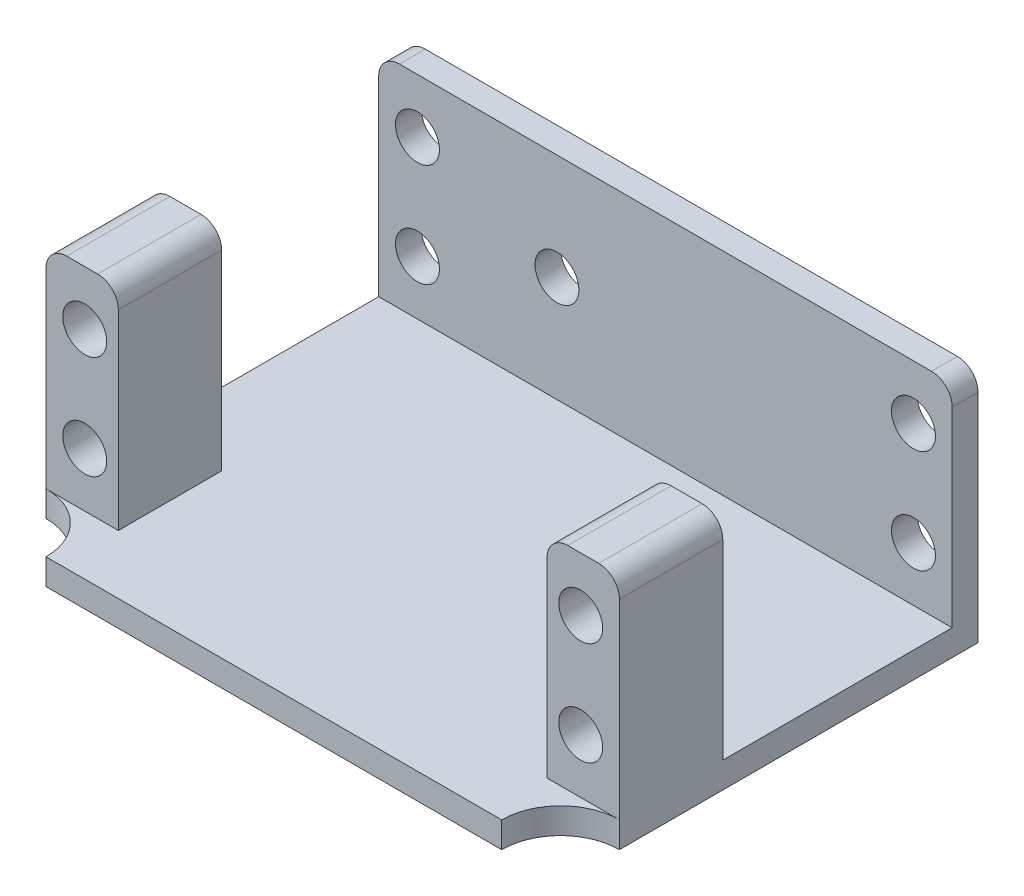
SolidWorks part; units mm, degrees
ref_plane "Front" through (0, 0, 0) normal (0, 0, 1) x (1, 0, 0)
ref_plane "Top" through (0, 0, 0) normal (0, 1, 0) x (1, 0, 0)
ref_plane "Right" through (0, 0, 0) normal (1, 0, 0) x (0, 0, -1)
sketch "Sketch1" plane through (0, 0, 0) normal (0, 1, 0) x (1, 0, 0)
  line L1 (0, 0) -> (55.5, 0)
  line L2 (0, 0) -> (0, 37.9)
  line L3 (0, 37.9) -> (55.5, 37.9)
  line L4 (55.5, 0) -> (55.5, 37.9)
  dimension "D1" = 37.9
  dimension "D2" = 55.5
extrude "bracketBase" add sketch "Sketch1" along normal blind 2.5
ref_plane "referencePlane1" through (0, 0, -8.2) normal (0, 0, 1) x (1, 0, 0)
sketch "Sketch2" plane through (0, 0, -8.2) normal (0, 0, 1) x (1, 0, 0)
  line L0 (27.75, 2.5) -> (27.75, 23) construction
  line L1 (0, 2.5) -> (7, 2.5)
  line L2 (0, 2.5) -> (0, 23)
  line L3 (0, 23) -> (7, 23)
  line L4 (7, 2.5) -> (7, 23)
  line L5 (0, 2.5) -> (55.5, 2.5) construction
  line L6 (55.5, 23) -> (48.5, 23)
  line L7 (48.5, 2.5) -> (48.5, 23)
  line L8 (55.5, 2.5) -> (48.5, 2.5)
  line L9 (55.5, 2.5) -> (55.5, 23)
  dimension "D1" = 20.5
  dimension "D2" = 7
extrude "servoMountingHoleTabs" add sketch "Sketch2" along normal blind 2.5
sketch "Sketch3" plane through (0, 0, -5.7) normal (0, 0, 1) x (1, 0, 0)
  line L0 (0, 12.75) -> (7, 12.75) construction
  line L3 (0, 23) -> (0, 2.5) construction
  line L4 (7, 2.5) -> (7, 23) construction
  line L5 (7, 23) -> (0, 23) construction
  line L6 (27.75, 2.5) -> (27.75, 23) construction
  line L7 (0, 2.5) -> (55.5, 2.5) construction
  circle A0 centre (3.75, 17.75) radius 2.125
  circle A1 centre (3.75, 7.75) radius 2.125
  circle A2 centre (51.75, 7.75) radius 2.125
  circle A3 centre (51.75, 17.75) radius 2.125
  dimension "D1" = 4.25
  dimension "D2" = 3.75
  dimension "D3" = 5.25
extrude "servoMountingHoles" cut sketch "Sketch3" against normal blind 2.5
sketch "Sketch4" plane through (0, 0, 0) normal (0, 1, 0) x (1, 0, 0)
  line L0 (55.5, 8.2) -> (55.5, 37.9) construction
  line L1 (0, 37.9) -> (55.5, 37.9)
  line L2 (0, 37.9) -> (0, 40.4)
  line L3 (0, 40.4) -> (55.5, 40.4)
  line L4 (55.5, 37.9) -> (55.5, 40.4)
  dimension "D1" = 2.5
extrude "baseWall" add sketch "Sketch4" along normal up to surface (23 mm away) up to face at (3.5, 23, -6.95)
sketch "Sketch6" plane through (0, 2.5, 0) normal (0, 1, 0) x (1, 0, 0)
  circle A0 centre (0, 0) radius 5.7
  circle A1 centre (55.5, 0) radius 5.7
extrude "baseTrim" cut sketch "Sketch6" against normal blind 2.5
fillet "Fillet1" radius 2 6 edges at (7, 23, -6.95) (48.5, 23, -6.95) (0, 23, -6.95) (55.5, 23, -6.95) (55.5, 23, -39.15) (0, 23, -39.15)
sketch "Sketch7" plane through (0, 0, -40.4) normal (0, 0, -1) x (-1, 0, 0)
  line L0 (0, 21) -> (0, 0) construction
  line L1 (-55.5, 0) -> (0, 0) construction
  circle A0 centre (-17.25, 12.75) radius 2.125
  dimension "D1" = 4.25
  dimension "D2" = 17.25
  dimension "D3" = 12.75
extrude "M4mountingHole" cut sketch "Sketch7" against normal blind 10
sketch "Sketch8" plane through (0, 0, -8.2) normal (0, 0, -1) x (-1, 0, 0)
  line L4 (-48.5, 2.5) -> (-48.5, 21)
  line L5 (-50.5, 23) -> (-53.5, 23)
  line L6 (-55.5, 21) -> (-55.5, 2.5)
  line L7 (-55.5, 2.5) -> (-48.5, 2.5)
  line L8 (-48.5, 2.5) -> (-48.5, 21)
  line L9 (-50.5, 23) -> (-53.5, 23)
  line L10 (-55.5, 21) -> (-55.5, 2.5)
  line L11 (-55.5, 2.5) -> (-48.5, 2.5)
  line L12 (-2, 23) -> (-5, 23)
  line L13 (-7, 21) -> (-7, 2.5)
  line L14 (-7, 2.5) -> (0, 2.5)
  line L15 (0, 2.5) -> (0, 21)
  line L16 (-2, 23) -> (-5, 23)
  line L17 (-7, 21) -> (-7, 2.5)
  line L18 (-7, 2.5) -> (0, 2.5)
  line L19 (0, 2.5) -> (0, 21)
  circle A0 centre (-51.75, 17.75) radius 2.125 construction
  circle A1 centre (-51.75, 17.75) radius 2.125
  arc A2 (-48.5, 21) -> (-50.5, 23) centre (-50.5, 21) ccw
  arc A3 (-53.5, 23) -> (-55.5, 21) centre (-53.5, 21) ccw
  arc A4 (-48.5, 21) -> (-50.5, 23) centre (-50.5, 21) ccw
  arc A5 (-53.5, 23) -> (-55.5, 21) centre (-53.5, 21) ccw
  arc A6 (-5, 23) -> (-7, 21) centre (-5, 21) ccw
  arc A7 (0, 21) -> (-2, 23) centre (-2, 21) ccw
  arc A8 (-5, 23) -> (-7, 21) centre (-5, 21) ccw
  arc A9 (0, 21) -> (-2, 23) centre (-2, 21) ccw
  circle A10 centre (-51.75, 7.75) radius 2.125 construction
  circle A11 centre (-51.75, 7.75) radius 2.125
  circle A12 centre (-3.75, 17.75) radius 2.125 construction
  circle A13 centre (-3.75, 17.75) radius 2.125
  circle A14 centre (-3.75, 7.75) radius 2.125 construction
  circle A15 centre (-3.75, 7.75) radius 2.125
  dimension "D1" = 0
  dimension "D2" = 0
extrude "Boss-Extrude1" add sketch "Sketch8" along normal blind 7.5
sketch "Sketch9" plane through (0, 0, -5.7) normal (0, 0, 1) x (1, 0, 0)
  circle A0 centre (3.75, 17.75) radius 2.125 construction
  circle A1 centre (3.75, 17.75) radius 2.125
  circle A2 centre (3.75, 7.75) radius 2.125 construction
  circle A3 centre (3.75, 7.75) radius 2.125
  circle A4 centre (51.75, 17.75) radius 2.125 construction
  circle A5 centre (51.75, 17.75) radius 2.125
  circle A6 centre (51.75, 7.75) radius 2.125 construction
  circle A7 centre (51.75, 7.75) radius 2.125
extrude "Cut-Extrude1" cut sketch "Sketch9" against normal through all
